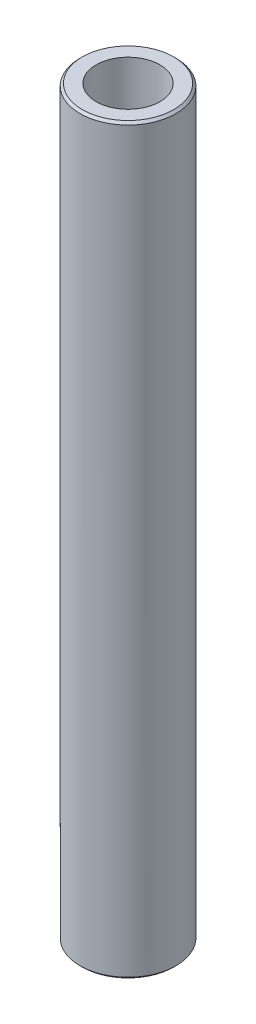
SolidWorks part; units mm, degrees
ref_plane "Front Plane" through (0, 0, 0) normal (0, 0, 1) x (1, 0, 0)
ref_plane "Top Plane" through (0, 0, 0) normal (0, 1, 0) x (1, 0, 0)
ref_plane "Right Plane" through (0, 0, 0) normal (1, 0, 0) x (0, 0, -1)
sketch "Sketch1" plane through (0, 0, 0) normal (0, 1, 0) x (1, 0, 0)
  circle A0 centre (0, 0) radius 30
  dimension "SHAFT_OD" = 60
extrude "Boss-Extrude1" add sketch "Sketch1" along normal blind 464.0653
sketch "Sketch2" plane through (0, 0, 0) normal (0, 1, 0) x (1, 0, 0)
  circle A0 centre (0, 0) radius 19.9633
  dimension "BORE_D" = 39.9266
extrude "Cut-Extrude1" cut sketch "Sketch2" along normal through all
chamfer "Chamfer1" distance 1.4399 angle 45 2 edges at (0, 464.0653, 30) (0, 0, 30)
